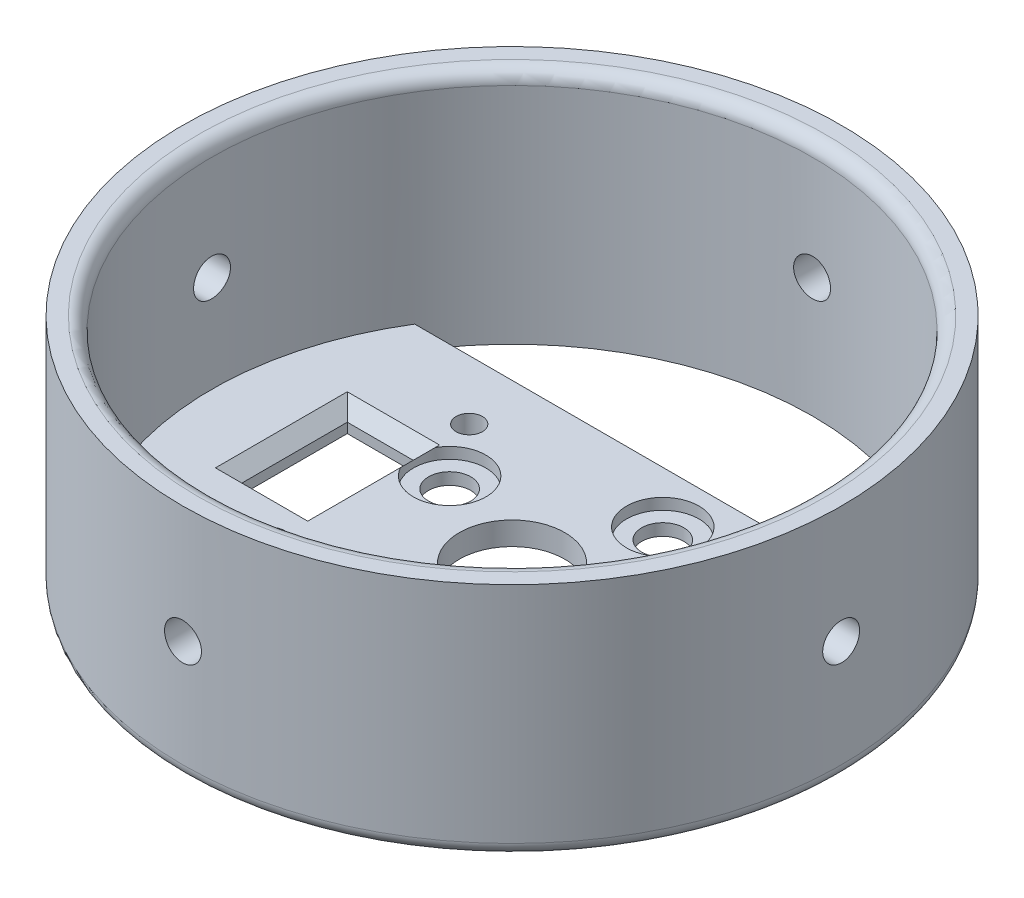
SolidWorks part; units mm, degrees
ref_plane "Front Plane" through (0, 0, 0) normal (0, 0, 1) x (1, 0, 0)
ref_plane "Top Plane" through (0, 0, 0) normal (0, 1, 0) x (1, 0, 0)
ref_plane "Right Plane" through (0, 0, 0) normal (1, 0, 0) x (0, 0, -1)
sketch "Sketch1" plane through (0, 0, 0) normal (0, 1, 0) x (1, 0, 0)
  line L0 (0, 8.75) -> (0, -8.75) construction
  line L1 (3.3485, 8.0839) -> (-3.3485, -8.0839) construction
  circle A0 centre (0, 0) radius 25
  circle A1 centre (0, 0) radius 4
  circle A2 centre (0, 0) radius 8.75 construction
  circle A3 centre (3.3485, 8.0839) radius 1.6
  circle A4 centre (8.0839, -3.3485) radius 1.6
  circle A5 centre (-3.3485, -8.0839) radius 1.6
  circle A6 centre (-8.0839, 3.3485) radius 1.6
  point P19 (0, 0)
  dimension "D1" = 50
  dimension "D2" = 8
  dimension "D3" = 17.5
  dimension "D5" = 3.2
  dimension "D4" = 22.5
  dimension "D6" = 4
extrude "Main Boss" add sketch "Sketch1" along normal blind 18
sketch "Sketch2" plane through (0, 18, 0) normal (0, 1, 0) x (1, 0, 0)
  circle A0 centre (0, 0) radius 22.8
  dimension "D1" = 45.6
extrude "Hollow" cut sketch "Sketch2" against normal offset from surface (16.25 mm away) 1.75 up to face at (0, 0, 25)
fillet "Fillet1" radius 1 2 edges at (0, 0, 25) (0, 18, 22.8)
sketch "Sketch3" plane through (0, 0, 0) normal (0, 0, 1) x (1, 0, 0)
  line L0 (25, 18) -> (-25, 18) construction
  circle A0 centre (0, 9.1) radius 1.4
  dimension "D2" = 2.8
  dimension "D1" = 8.9
extrude "External Screw Holes" cut sketch "Sketch3" against normal through all both and the other way through all
pattern_circular "CirPattern1" count 2 every 90 about axis through (0, -64.4881, 0) along (0, 1, 0) of "External Screw Holes"
sketch "Sketch4" plane through (0, 1.75, 0) normal (0, 1, 0) x (1, 0, 0)
  line L0 (-18.7307, 13) -> (18.7307, 13)
  line L1 (-18.7307, -13) -> (18.7307, -13)
  circle A0 centre (0, 0) radius 22.8 construction
  arc A1 (-18.7307, -13) -> (18.7307, -13) centre (0, 0) ccw
  arc A2 (18.7307, 13) -> (-18.7307, 13) centre (0, 0) ccw
  dimension "D1" = 26
extrude "Sensor Allowance" cut sketch "Sketch4" against normal through all
sketch "Sketch5" plane through (0, 1.75, 0) normal (0, 1, 0) x (1, 0, 0)
  line L0 (-16.5, 0) -> (16.5, 0) construction
  line L1 (-16.5, 4) -> (-11.5, 4)
  line L2 (-16.5, 4) -> (-16.5, -4)
  line L3 (-16.5, -4) -> (-11.5, -4)
  line L4 (-11.5, 4) -> (-11.5, -4)
  line L5 (11.5, 4) -> (16.5, 4)
  line L6 (11.5, 4) -> (11.5, -4)
  line L7 (11.5, -4) -> (16.5, -4)
  line L8 (16.5, 4) -> (16.5, -4)
  dimension "D1" = 5
  dimension "D2" = 8
  dimension "D3" = 23
extrude "Power Allowance" cut sketch "Sketch5" against normal through all
sketch "Sketch7" plane through (0, 0, 0) normal (0, -1, 0) x (1, 0, 0)
  line L0 (-12.5, -18.5) -> (1.75, -18.5)
  line L1 (-12.5, -18.5) -> (-12.5, -13)
  line L2 (1.75, -18.5) -> (1.75, -13)
  line L3 (-12.5, -13) -> (1.75, -13)
  line L4 (12.5, 13) -> (-1.75, 13)
  line L5 (12.5, -13) -> (12.5, -18.5)
  line L6 (12.5, -13) -> (2.25, -13)
  line L7 (12.5, -18.5) -> (2.25, -18.5)
  line L8 (2.25, -13) -> (2.25, -18.5)
  line L9 (-18.7307, -13) -> (18.7307, -13) construction
  line L10 (12.5, 18.5) -> (12.5, 13)
  line L11 (12.5, 18.5) -> (-1.75, 18.5)
  line L12 (-1.75, 18.5) -> (-1.75, 13)
  line L13 (-2.25, 13) -> (-2.25, 18.5)
  line L14 (-12.5, 13) -> (-2.25, 13)
  line L15 (-12.5, 18.5) -> (-2.25, 18.5)
  line L16 (-12.5, 13) -> (-12.5, 18.5)
  line L17 (18.7307, 13) -> (-18.7307, 13) construction
  line L18 (-12.5, -18.5) -> (-13.3263, -18.5) construction
  line L19 (12.5, -18.5) -> (13.3263, -18.5) construction
  line L20 (-12.5, 18.5) -> (-13.3263, 18.5) construction
  line L21 (12.5, 18.5) -> (13.3263, 18.5) construction
  arc A0 (-18.7307, -13) -> (18.7307, -13) centre (0, 0) ccw construction
  arc A1 (18.7307, 13) -> (-18.7307, 13) centre (0, 0) ccw construction
  point P23 (0, 0)
  dimension "D1" = 5.5
  dimension "D2" = 14.25
  dimension "D3" = 10.25
  dimension "D5" = 0.5
  dimension "D4" = 2
chamfer "Chamfer1" distance 1 angle 45 10 edges at (-14, 1.75, -4) (-16.5, 1.75, 0) (-14, 1.75, 4) (-11.5, 1.75, 0) (14, 1.75, -4) (16.5, 1.75, 0) (14, 1.75, 4) (11.5, 1.75, 0) (0, 1.75, -13) (0, 1.75, 13)
sketch "Sketch8" plane through (0, 1.75, 0) normal (0, 1, 0) x (1, 0, 0)
  line L0 (-10.75, 7.5) -> (10.75, 7.5) construction
  line L1 (10.75, 7.5) -> (10.75, -7.5) construction
  line L2 (10.75, -7.5) -> (-10.75, -7.5) construction
  line L3 (-10.75, -7.5) -> (-10.75, 7.5) construction
  line L4 (-10.75, 7.5) -> (10.75, -7.5) construction
  circle A0 centre (-10.75, 7.5) radius 1
  circle A1 centre (10.75, 7.5) radius 1
  circle A2 centre (-10.75, -7.5) radius 1
  circle A3 centre (10.75, -7.5) radius 1
  point P8 (0, 0)
  dimension "D3" = 2
  dimension "D1" = 15
  dimension "D2" = 21.5
extrude "Cut-Extrude1" cut sketch "Sketch8" against normal through all
sketch "Sketch9" plane through (0, 1.75, 0) normal (0, 1, 0) x (1, 0, 0)
  circle A0 centre (-8.0839, 3.3485) radius 2.75
  circle A1 centre (3.3485, 8.0839) radius 2.75
  circle A2 centre (8.0839, -3.3485) radius 2.75
  circle A3 centre (-3.3485, -8.0839) radius 2.75
  circle A4 centre (-3.3485, -8.0839) radius 1.6 construction
  circle A5 centre (8.0839, -3.3485) radius 1.6 construction
  circle A6 centre (3.3485, 8.0839) radius 1.6 construction
  circle A7 centre (-8.0839, 3.3485) radius 1.6 construction
  dimension "D1" = 5.5
extrude "Cut-Extrude2" cut sketch "Sketch9" against normal blind 0.85
